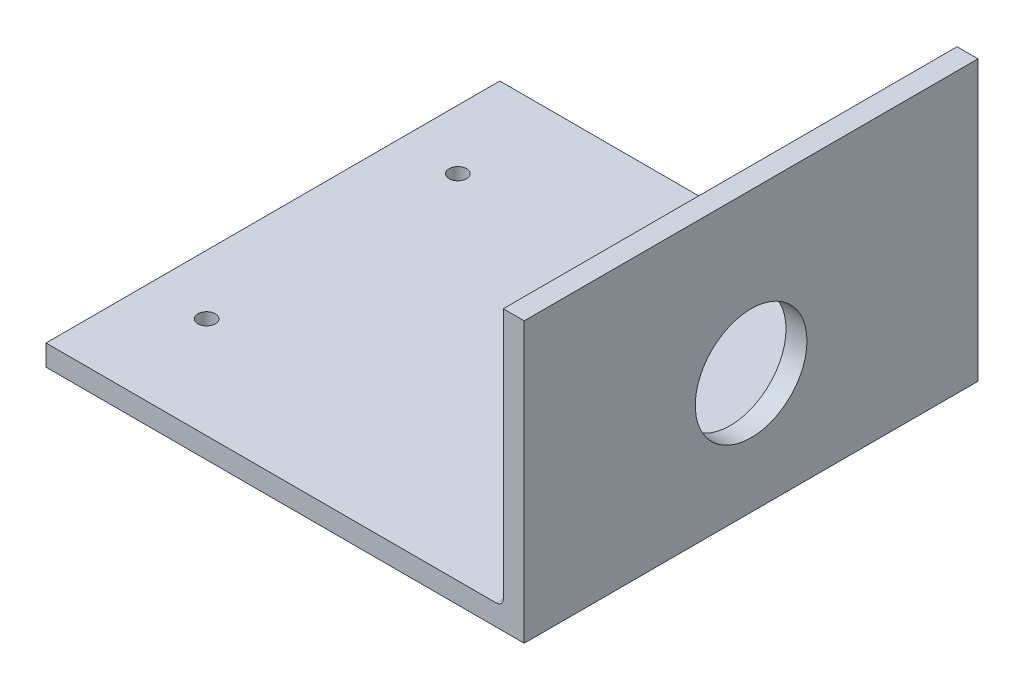
SolidWorks part; units mm, degrees
material "7075-T6 (SN)"
ref_plane "Front Plane" through (0, 0, 0) normal (0, 0, 1) x (1, 0, 0)
ref_plane "Top Plane" through (0, 0, 0) normal (0, 1, 0) x (1, 0, 0)
ref_plane "Right Plane" through (0, 0, 0) normal (1, 0, 0) x (0, 0, -1)
sketch "Sketch3" plane through (0, 863.6295, 0) normal (0, -1, 0) x (1, 0, 0)
  line L1 (652.732, 1341.8329) -> (717.732, 1341.8329)
  line L2 (652.732, 1341.8329) -> (652.732, 1276.8329)
  line L3 (652.732, 1276.8329) -> (717.732, 1276.8329)
  line L4 (717.732, 1341.8329) -> (717.732, 1276.8329)
  line L5 (652.732, 1341.8329) -> (717.732, 1276.8329) construction
  line L6 (652.732, 1276.8329) -> (717.732, 1341.8329) construction
  arc A0 (659.982, 1327.3329) -> (661.232, 1326.0829) centre (661.232, 1327.3329) ccw construction
  arc A1 (661.232, 1328.5829) -> (659.982, 1327.3329) centre (661.232, 1327.3329) ccw construction
  arc A2 (662.482, 1327.3329) -> (661.232, 1328.5829) centre (661.232, 1327.3329) ccw construction
  arc A3 (661.232, 1326.0829) -> (662.482, 1327.3329) centre (661.232, 1327.3329) ccw construction
  arc A4 (659.982, 1327.3329) -> (661.232, 1326.0829) centre (661.232, 1327.3329) ccw
  arc A5 (661.232, 1328.5829) -> (659.982, 1327.3329) centre (661.232, 1327.3329) ccw
  arc A6 (662.482, 1327.3329) -> (661.232, 1328.5829) centre (661.232, 1327.3329) ccw
  arc A7 (661.232, 1326.0829) -> (662.482, 1327.3329) centre (661.232, 1327.3329) ccw
  arc A8 (659.982, 1291.3329) -> (661.232, 1290.0829) centre (661.232, 1291.3329) ccw construction
  arc A9 (661.232, 1290.0829) -> (662.482, 1291.3329) centre (661.232, 1291.3329) ccw construction
  arc A10 (662.482, 1291.3329) -> (661.232, 1292.5829) centre (661.232, 1291.3329) ccw construction
  arc A11 (661.232, 1292.5829) -> (659.982, 1291.3329) centre (661.232, 1291.3329) ccw construction
  arc A12 (707.982, 1291.3329) -> (709.232, 1290.0829) centre (709.232, 1291.3329) ccw construction
  arc A13 (709.232, 1290.0829) -> (710.482, 1291.3329) centre (709.232, 1291.3329) ccw construction
  arc A14 (710.482, 1291.3329) -> (709.232, 1292.5829) centre (709.232, 1291.3329) ccw construction
  arc A15 (709.232, 1292.5829) -> (707.982, 1291.3329) centre (709.232, 1291.3329) ccw construction
  arc A16 (707.982, 1327.3329) -> (709.232, 1326.0829) centre (709.232, 1327.3329) ccw construction
  arc A17 (709.232, 1328.5829) -> (707.982, 1327.3329) centre (709.232, 1327.3329) ccw construction
  arc A18 (710.482, 1327.3329) -> (709.232, 1328.5829) centre (709.232, 1327.3329) ccw construction
  arc A19 (709.232, 1326.0829) -> (710.482, 1327.3329) centre (709.232, 1327.3329) ccw construction
  arc A20 (659.982, 1291.3329) -> (661.232, 1290.0829) centre (661.232, 1291.3329) ccw
  arc A21 (661.232, 1290.0829) -> (662.482, 1291.3329) centre (661.232, 1291.3329) ccw
  arc A22 (662.482, 1291.3329) -> (661.232, 1292.5829) centre (661.232, 1291.3329) ccw
  arc A23 (661.232, 1292.5829) -> (659.982, 1291.3329) centre (661.232, 1291.3329) ccw
  arc A24 (707.982, 1291.3329) -> (709.232, 1290.0829) centre (709.232, 1291.3329) ccw
  arc A25 (709.232, 1290.0829) -> (710.482, 1291.3329) centre (709.232, 1291.3329) ccw
  arc A26 (710.482, 1291.3329) -> (709.232, 1292.5829) centre (709.232, 1291.3329) ccw
  arc A27 (709.232, 1292.5829) -> (707.982, 1291.3329) centre (709.232, 1291.3329) ccw
  arc A28 (707.982, 1327.3329) -> (709.232, 1326.0829) centre (709.232, 1327.3329) ccw
  arc A29 (709.232, 1328.5829) -> (707.982, 1327.3329) centre (709.232, 1327.3329) ccw
  arc A30 (710.482, 1327.3329) -> (709.232, 1328.5829) centre (709.232, 1327.3329) ccw
  arc A31 (709.232, 1326.0829) -> (710.482, 1327.3329) centre (709.232, 1327.3329) ccw
  point P0 (685.232, 1309.3329)
  dimension "D1" = 65
  dimension "D2" = 65
extrude "Boss-Extrude2" add sketch "Sketch3" along normal blind 3
sketch "Sketch4" plane through (0, 0, 1276.8329) normal (0, 0, -1) x (-1, 0, 0)
  line L0 (-717.732, 860.6295) -> (-717.732, 863.6295) construction
  line L1 (-717.732, 860.6295) -> (-717.732, 863.6295)
  line L2 (-717.732, 863.6295) -> (-718.232, 863.6295)
  line L3 (-718.232, 863.6295) -> (-718.232, 900.6295)
  line L4 (-718.232, 900.6295) -> (-721.232, 900.6295)
  line L5 (-721.232, 900.6295) -> (-721.232, 860.6295)
  line L6 (-721.232, 860.6295) -> (-717.732, 860.6295)
  line L7 (-652.732, 860.6295) -> (-652.732, 863.6295) construction
  dimension "D1" = 0.5
  dimension "D2" = 40
extrude "Boss-Extrude3" add sketch "Sketch4" against normal up to surface (65 mm away) up to face at (685.232, 862.1295, 1341.8329)
sketch "Sketch6" plane through (721.232, 0, 0) normal (1, 0, 0) x (0, 0, -1)
  arc A0 (-1309.3329, 871.8795) -> (-1309.3329, 883.8795) centre (-1309.3329, 877.8795) ccw construction
  arc A1 (-1309.3329, 883.8795) -> (-1309.3329, 871.8795) centre (-1309.3329, 877.8795) ccw construction
  arc A2 (-1309.3329, 871.8795) -> (-1309.3329, 883.8795) centre (-1309.3329, 877.8795) ccw construction
  arc A3 (-1309.3329, 883.8795) -> (-1309.3329, 871.8795) centre (-1309.3329, 877.8795) ccw construction
  circle A4 centre (-1309.3329, 877.8795) radius 8
  dimension "D1" = 16
extrude "Cut-Extrude1" cut sketch "Sketch6" against normal up to next
fillet "Fillet1" radius 1 1 edges at (718.232, 863.6295, 1309.3329)
